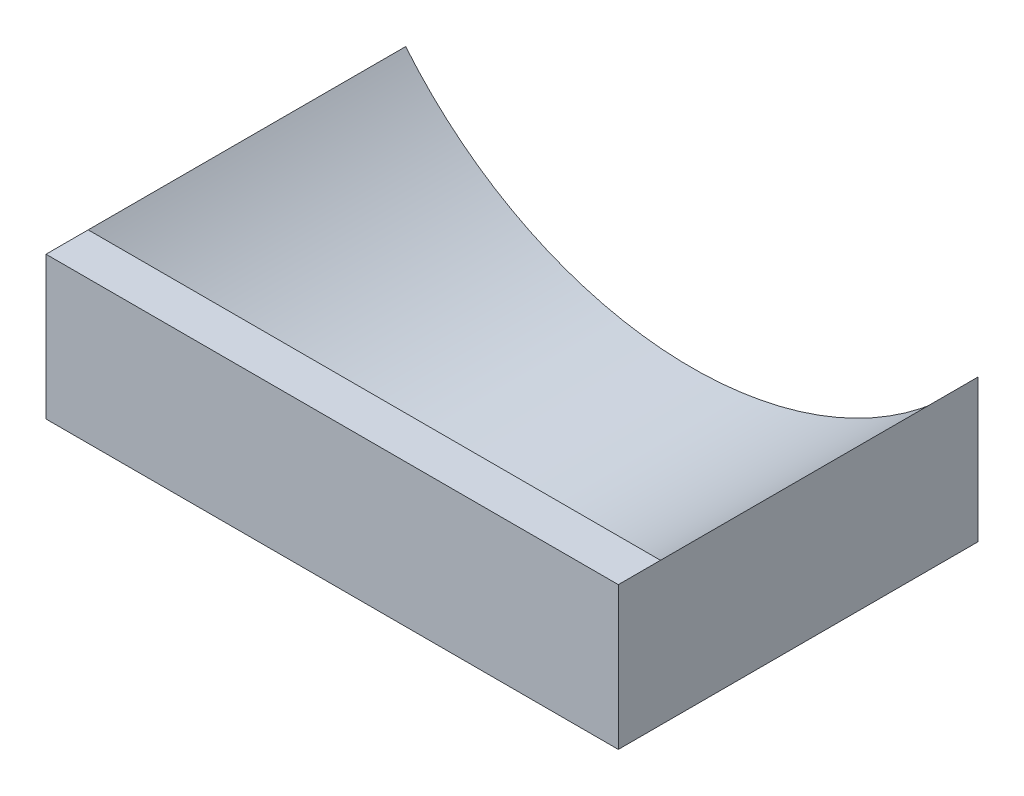
SolidWorks part; units mm, degrees
ref_plane "Front Plane" through (0, 0, 0) normal (0, 0, 1) x (1, 0, 0)
ref_plane "Top Plane" through (0, 0, 0) normal (0, 1, 0) x (1, 0, 0)
ref_plane "Right Plane" through (0, 0, 0) normal (1, 0, 0) x (0, 0, -1)
sketch "Sketch1" plane through (0, 0, 0) normal (0, 0, 1) x (1, 0, 0)
  line L3 (-10.7708, -14.2375) -> (10.7708, -14.2375)
  line L7 (10.7708, -8.8652) -> (10.7708, -14.2375)
  line L8 (-10.7708, -8.8652) -> (-10.7708, -14.2375)
  arc A0 (-10.7708, -8.8652) -> (10.7708, -8.8652) centre (0, 0) ccw
  arc A1 (10.7708, -8.8652) -> (-10.7708, -8.8652) centre (0, 0) cw
  dimension "D1" = 27.9
  dimension "D3" = 21.5416
  dimension "D5" = 5.3723
  dimension "D6" = 5.3723
extrude "Boss-Extrude1" add sketch "Sketch1" along normal blind 11.95 contours A0 L8 L3 L7 region at (-10.5488, -11.5514, 0)
sketch "Sketch2" plane through (0, 0, 11.95) normal (0, 0, 1) x (1, 0, 0)
  line L1 (-10.7708, -8.8652) -> (10.7708, -8.8652)
  line L2 (-10.7708, -8.8652) -> (-10.7708, -14.2375)
  line L3 (-10.7708, -14.2375) -> (10.7708, -14.2375)
  line L4 (10.7708, -8.8652) -> (10.7708, -14.2375)
extrude "Boss-Extrude2" add sketch "Sketch2" along normal blind 1.5875
